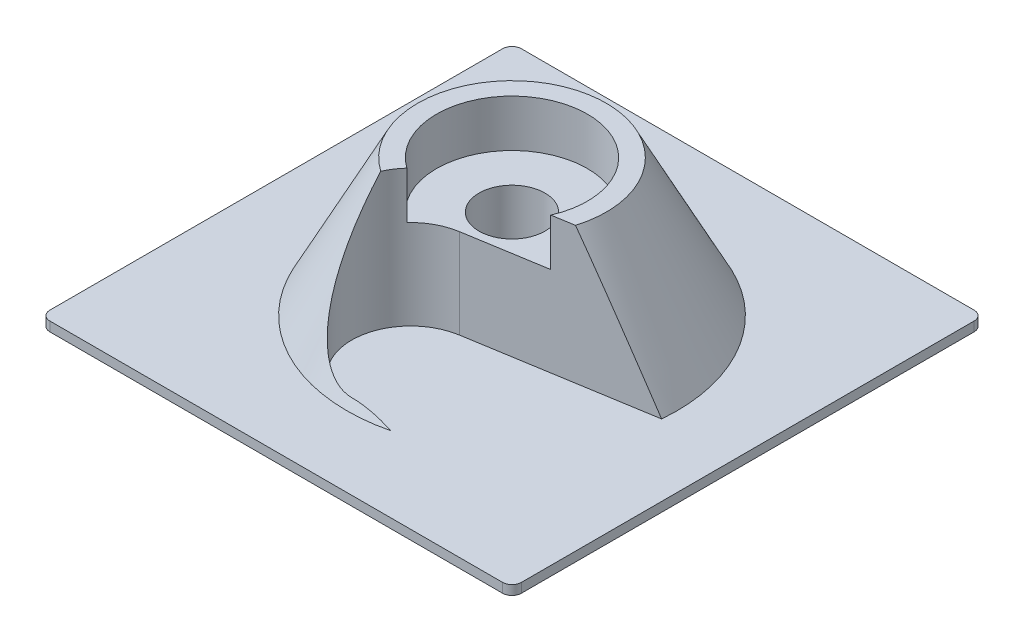
SolidWorks part; units mm, degrees
ref_plane "Front Plane" through (0, 0, 0) normal (0, 0, 1) x (1, 0, 0)
ref_plane "Top Plane" through (0, 0, 0) normal (0, 1, 0) x (1, 0, 0)
ref_plane "Right Plane" through (0, 0, 0) normal (1, 0, 0) x (0, 0, -1)
sketch "Sketch1" plane through (0, 0, 0) normal (0, 1, 0) x (1, 0, 0)
  line L0 (-25, 25) -> (25, -25) construction
  line L1 (-24, 25) -> (24, 25)
  line L2 (-25, 24) -> (-25, -24)
  line L3 (-24, -25) -> (24, -25)
  line L4 (25, 24) -> (25, -24)
  arc A0 (24, 25) -> (25, 24) centre (24, 24) cw
  arc A1 (-25, -24) -> (-24, -25) centre (-24, -24) ccw
  arc A2 (24, -25) -> (25, -24) centre (24, -24) ccw
  arc A3 (-24, 25) -> (-25, 24) centre (-24, 24) ccw
  circle A4 centre (0, 0) radius 3.5
  point P7 (25, 25)
  dimension "D2" = 1
  dimension "D3" = 7
  dimension "D1" = 50
extrude "Boss-Extrude1" add sketch "Sketch1" along normal blind 0.5 and the other way blind 0.5
sketch "Sketch2" plane through (0, 0, 0) normal (0, 0, 1) x (1, 0, 0)
  line L0 (0, 0.5) -> (0, 15) construction
  line L1 (-24, 0.5) -> (24, 0.5) construction
  line L2 (-8, 15) -> (-10, 15)
  line L3 (-10, 15) -> (-17.5, 0.5)
  line L4 (-8, 15) -> (-8, 10)
  line L5 (-8, 10) -> (-3.5, 10)
  line L6 (-3.5, 10) -> (-3.5, 0.5)
  line L7 (-3.5, 0.5) -> (-17.5, 0.5)
  dimension "D1" = 14.5
  dimension "D2" = 10
  dimension "D3" = 7.5
  dimension "D4" = 2
  dimension "D5" = 5
  dimension "D6" = 4.5
revolve "Revolve1" add sketch "Sketch2" angle 360 about L0 other way angle 360
sketch "Sketch4" plane through (0, 15, 0) normal (0, 1, 0) x (1, 0, 0)
  line L0 (25, -0.3243) -> (-1.0097, -4.5821)
  line L1 (25, -0.3243) -> (25, -7.125)
  line L3 (0, -17) -> (25, -17)
  line L5 (25, -17) -> (25, -7.125)
  arc A0 (-1.0097, -4.5821) -> (0, -17) centre (0, -10.75) ccw
  arc A3 (-1.0097, -4.5821) -> (4.0276, -15.5292) centre (0, -10.75) ccw construction
extrude "Cut-Extrude1" cut sketch "Sketch4" against normal up to surface (14.5 mm away) up to face at (0, 0.5, 0)
